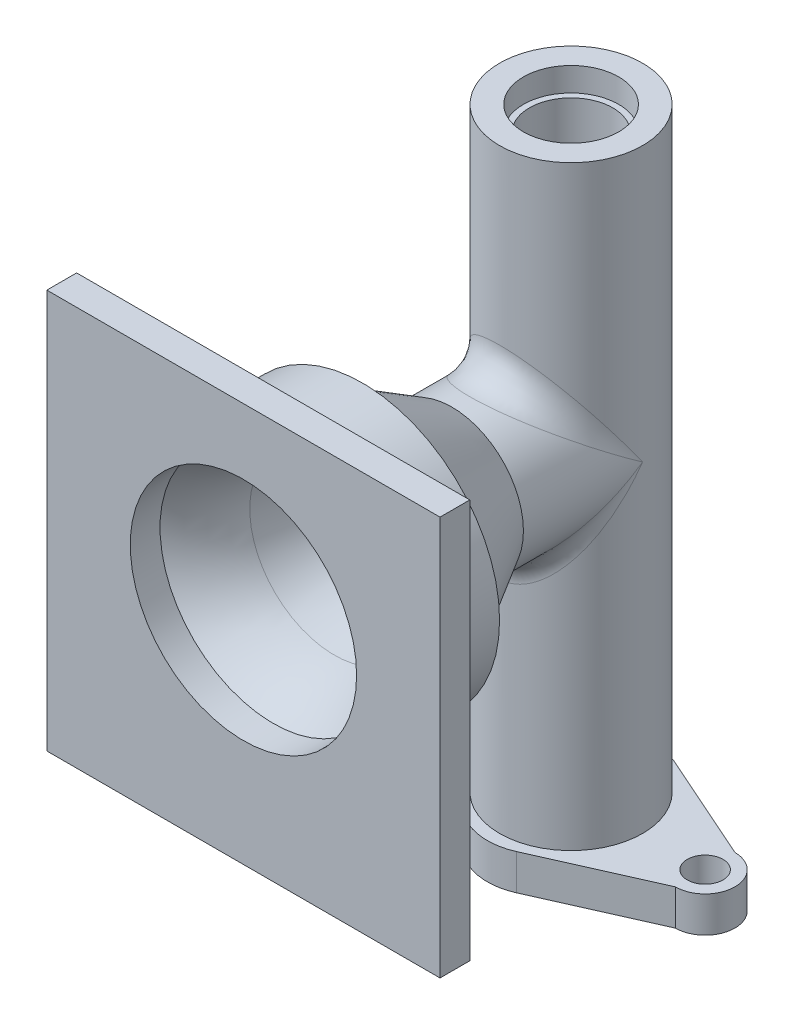
SolidWorks part; units mm, degrees
material "6063-T1"
ref_plane "Спереди" through (0, 0, 0) normal (0, 0, 1) x (1, 0, 0)
ref_plane "Сверху" through (0, 0, 0) normal (0, 1, 0) x (1, 0, 0)
ref_plane "Справа" through (0, 0, 0) normal (1, 0, 0) x (0, 0, -1)
sketch "Эскиз1" plane through (0, 0, 0) normal (0, 1, 0) x (1, 0, 0)
  line L0 (0, 0) -> (22.5, 0) construction
  line L1 (22.5, 0) -> (45, 0) construction
  line L2 (22.5, 0) -> (22.5, 15) construction
  line L3 (22.5, 0) -> (22.5, -15) construction
  line L4 (0, 0) -> (0, 5) construction
  line L5 (0, 0) -> (0, -5) construction
  line L6 (45, 0) -> (45, 5) construction
  line L7 (45, 0) -> (45, -5) construction
  line L8 (0, 5) -> (22.5, 15)
  line L9 (22.5, 15) -> (45, 5)
  line L10 (45, -5) -> (22.5, -15)
  line L11 (22.5, -15) -> (0, -5)
  circle A0 centre (0, 0) radius 3
  circle A1 centre (22.5, 0) radius 10
  circle A2 centre (45, 0) radius 3
  arc A3 (0, 5) -> (0, -5) centre (0, 0) ccw
  arc A4 (45, 5) -> (45, -5) centre (45, 0) cw
  dimension "D1" = 6
  dimension "D2" = 20
  dimension "D3" = 22.5
  dimension "D4" = 15
  dimension "D5" = 5
extrude "Бобышка-Вытянуть1" add sketch "Эскиз1" along normal blind 6 contours A4 L9 L8 A3 L11 L10 A2 A1 A0
fillet "Скругление1" radius 10 1 edges at (22.5, 3, 15)
fillet "Скругление2" radius 10 1 edges at (22.5, 3, -15)
sketch "Эскиз2" plane through (0, 6, 0) normal (0, 1, 0) x (1, 0, 0)
  circle A0 centre (22.5, 0) radius 12
  circle A1 centre (22.5, 0) radius 10
  dimension "D1" = 24
  dimension "D2" = 20
extrude "Бобышка-Вытянуть2" add sketch "Эскиз2" along normal blind 85
sketch "Эскиз3" plane through (0, 91, 0) normal (0, 1, 0) x (1, 0, 0)
  circle A0 centre (22.5, 0) radius 12
  dimension "D1" = 24
extrude "Бобышка-Вытянуть3" add sketch "Эскиз3" along normal blind 15
sketch "Эскиз4" plane through (0, 106, 0) normal (0, 1, 0) x (1, 0, 0)
  circle A0 centre (22.5, 0) radius 4
  dimension "D1" = 8
extrude "Вырез-Вытянуть1" cut sketch "Эскиз4" against normal through all
sketch "Эскиз6" plane through (0, 106, 0) normal (0, 1, 0) x (1, 0, 0)
  circle A0 centre (22.5, 0) radius 7
  dimension "D1" = 14
extrude "Вырез-Вытянуть2" cut sketch "Эскиз6" against normal blind 12
sketch "Эскиз7" plane through (0, 106, 0) normal (0, 1, 0) x (1, 0, 0)
  circle A0 centre (22.5, 0) radius 8
  dimension "D1" = 16
extrude "Вырез-Вытянуть3" cut sketch "Эскиз7" against normal blind 4
sketch3d "Трехмерный эскиз4"
  line L0 (0, 0, 0) -> (45, 0, 0) construction
  line L1 (45, 6, 0) -> (45, 0, 0) construction
  line L2 (45, 0, 0) -> (45, 63.4689, 0) construction
  line L3 (45, 63.4689, 0) -> (0, 63.4689, 0) construction
  line L4 (0, 63.4689, 0) -> (0, 0, 0) construction
  line L5 (22.5, 0, 0) -> (22.5, 60, 0)
  dimension "D1" = 60
sketch "Эскиз12" plane through (0, 0, 0) normal (0, 0, 1) x (1, 0, 0)
  circle A0 centre (22.5, 60) radius 12
  dimension "D1" = 24
extrude "Бобышка-Вытянуть4" add sketch "Эскиз12" along normal blind 35
sketch "Эскиз13" plane through (0, 0, 0) normal (0, -1, 0) x (1, 0, 0)
  circle A0 centre (22.5, 0) radius 10
extrude "Вырез-Вытянуть4" cut sketch "Эскиз13" against normal blind 85
sketch "Эскиз14" plane through (0, 0, 35) normal (0, 0, 1) x (1, 0, 0)
  circle A0 centre (22.5, 60) radius 23
  dimension "D1" = 46
extrude "Бобышка-Вытянуть5" add sketch "Эскиз14" along normal blind 15
sketch "Эскиз15" plane through (0, 0, 50) normal (0, 0, 1) x (1, 0, 0)
  circle A0 centre (22.5, 60) radius 19
  dimension "D1" = 38
sketch "Эскиз16" plane through (0, 0, 50) normal (0, 0, 1) x (1, 0, 0)
  circle A0 centre (22.5, 60) radius 10
  dimension "D1" = 20
extrude "Вырез-Вытянуть8" cut sketch "Эскиз16" against normal blind 50 contours A0
chamfer "Фаска4" distance 15 angle 30 1 edges at (34.5, 60, 35)
sketch "Эскиз17" plane through (0, 0, 50) normal (0, 0, 1) x (1, 0, 0)
  line L0 (22.5, 60) -> (-10.5, 60) construction
  line L1 (22.5, 60) -> (55.5, 60) construction
  line L2 (22.5, 60) -> (22.5, 23) construction
  line L3 (22.5, 0) -> (22.5, 60) construction
  line L4 (22.5, 60) -> (22.5, 90) construction
  line L5 (55.5, 90) -> (-10.5, 90)
  line L6 (-10.5, 90) -> (-10.5, 23)
  line L7 (-10.5, 23) -> (55.5, 23)
  line L8 (55.5, 23) -> (55.5, 90)
  dimension "D1" = 33
  dimension "D2" = 37
  dimension "D3" = 30
extrude "Бобышка-Вытянуть6" add sketch "Эскиз17" along normal blind 5
extrude "Вырез-Вытянуть9" cut sketch "Эскиз15" along normal through all
chamfer "Фаска5" distance 5 angle 30 1 edges at (45.5, 60, 50)
fillet "Скругление9" radius 5 2 edges at (22.5, 72, 12) (22.5, 48, 12)
sketch3d "Трехмерный эскиз8"
  line L0 (22.5, 60, 0) -> (22.5, 60, 50) construction
  line L1 (22.5, 60, 0) -> (22.5, 60, 50) construction
  line L2 (22.5, 60, 55) -> (22.5, 60, 50) construction
sketch "Эскиз24" plane through (0, 0, 0) normal (0, 0, 1) x (1, 0, 0)
  circle A0 centre (22.5, 60) radius 10 construction
  dimension "D1" = 20
chamfer "Фаска9" distance 30 angle 12 1 edges at (32.5, 60, 50)
fillet "Скругление15" radius 25 1 edges at (38.8767, 60, 50)
